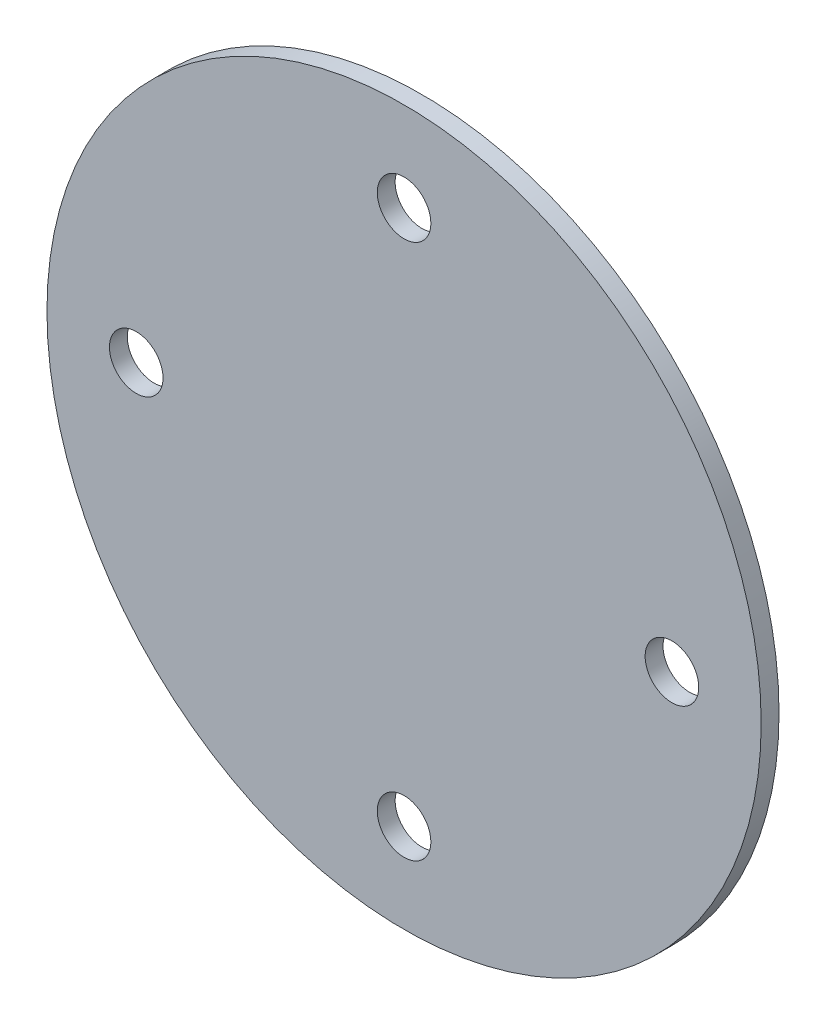
SolidWorks part; units mm, degrees
material "1060 合金"
ref_plane "前视基准面" through (0, 0, 0) normal (0, 0, 1) x (1, 0, 0)
ref_plane "上视基准面" through (0, 0, 0) normal (0, 1, 0) x (1, 0, 0)
ref_plane "右视基准面" through (0, 0, 0) normal (1, 0, 0) x (0, 0, -1)
sketch "草图1" plane through (0, 0, 0) normal (0, 0, 1) x (1, 0, 0)
  circle A0 centre (0, 0) radius 40
  dimension "D1" = 80
extrude "凸台-拉伸1" add sketch "草图1" along normal blind 2
sketch "草图2" plane through (0, 0, 2) normal (0, 0, 1) x (1, 0, 0)
  line L0 (0, 30) -> (0, 0) construction
  line L1 (0, 0) -> (0, -30) construction
  line L2 (-30, 0) -> (0, 0) construction
  line L3 (0, 0) -> (30, 0) construction
  circle A0 centre (30, 0) radius 3
  circle A1 centre (0, 30) radius 3
  circle A2 centre (-30, 0) radius 3
  circle A3 centre (0, -30) radius 3
  dimension "D1" = 6
  dimension "D2" = 6
  dimension "D7" = 6
  dimension "D8" = 6
  dimension "D3" = 30
  dimension "D4" = 30
  dimension "D5" = 30
  dimension "D6" = 30
extrude "切除-拉伸1" cut sketch "草图2" against normal through all
